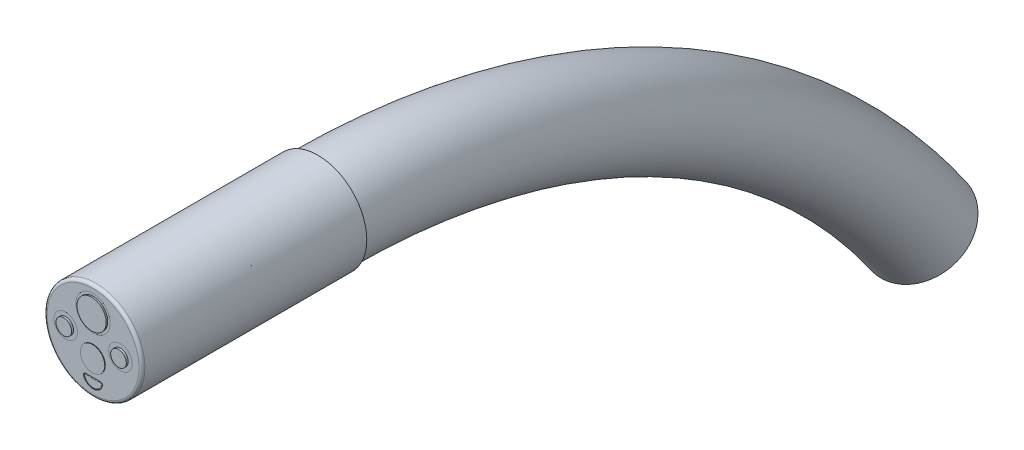
SolidWorks part; units mm, degrees
note: The reader was unsure of these and kept them because the rebuilt part matched: shared geometry of "Sketch", "Sketch", "Sketch", "Sketch", "Sketch", "Sketch", "Sketch", "Sketch", "Sketch", "Sketch".
ref_plane "Front" through (0, 0, 0) normal (0, 0, 1) x (1, 0, 0)
ref_plane "Top" through (0, 0, 0) normal (0, 1, 0) x (1, 0, 0)
ref_plane "Right" through (0, 0, 0) normal (1, 0, 0) x (0, 0, -1)
sketch "Sketch1" plane through (0, 0, 0) normal (0, 0, 1) x (1, 0, 0)
  circle A0 centre (0, 0) radius 5
  dimension "D1" = 10
extrude "Extrude1" add sketch "Sketch1" along normal blind 23
sketch "Sketch2" plane through (0, 0, 23) normal (0, 0, 1) x (1, 0, 0)
  line L0 (-0.7746, -3.2) -> (0.7746, -3.2)
  line L1 (0, 0) -> (0, 1.8906) construction
  circle A0 centre (0, 2.5) radius 1.5
  circle A1 centre (2.8, 0) radius 1
  circle A2 centre (0, -1.5) radius 1.25
  arc A3 (-0.9682, -3.45) -> (0.9682, -3.45) centre (0, -3.2) ccw
  arc A4 (-0.7746, -3.2) -> (-0.9682, -3.45) centre (-0.7746, -3.4) ccw
  arc A5 (0.7746, -3.2) -> (0.9682, -3.45) centre (0.7746, -3.4) cw
  circle A6 centre (-2.8, 0) radius 1
  point P13 (-1, -3.2)
  point P16 (1, -3.2)
  dimension "D1" = 3
  dimension "D2" = 2
  dimension "D3" = 2.5
  dimension "D7" = 2
  dimension "D9" = 0.2
  dimension "D10" = 0.2
  dimension "D4" = 2.5
  dimension "D5" = 2.8
  dimension "D6" = 1.5
  dimension "D8" = 3.2
extrude "Extrude2" cut sketch "Sketch2" against normal blind 40
sketch "Sketch3" plane through (0, 0, 0) normal (1, 0, 0) x (0, 0, -1)
  line L0 (0, -5) -> (0, 5) construction
  line L1 (0, 4) -> (-10.95, 4)
  line L2 (0, 4) -> (0, 3.3)
  line L3 (0, 3.3) -> (-10.95, 3.3)
  line L4 (-10.95, 4) -> (-10.95, 3.3)
  line L5 (0, 2.5) -> (-23, 2.5) construction
  line L6 (-23, 5) -> (-23, -5) construction
  line L7 (-10.95, 4) -> (-13.45, 4)
  line L8 (-10.95, 4) -> (-10.95, 4.25)
  line L9 (-10.95, 4.25) -> (-13.45, 4.25)
  line L10 (-13.45, 4) -> (-13.45, 4.25)
  line L11 (-4.2338, 2.5) -> (-7.2586, 2.5) construction
  dimension "D1" = 0.7
  dimension "D2" = 1.5
  dimension "D3" = 0.25
  dimension "D4" = 2.5
  dimension "D5" = 9.55
revolve "Revolve1" add sketch "Sketch3" angle 360 about L11
revolve "Cut-Revolve1" cut sketch "Sketch" angle 360 about L11
sketch "Sketch" plane through (0, 0, 0) normal (1, 0, 0) x (0, 0, -1) same geometry as "Sketch3"
sketch "Sketch4" plane through (0, 0, 23) normal (0, 0, 1) x (1, 0, 0)
  circle A2 centre (0, 2.5) radius 1.75
  circle A3 centre (0, 2.5) radius 1.75
  dimension "D1" = 0.25
extrude "Extrude3" cut sketch "Sketch4" against normal up to surface (9.55 mm away) up to face at (-1.75, 2.5, 13.45)
ref_plane "Plane1" through (-2.8, 0, 0) normal (1, 0, 0) x (0, 0, -1)
sketch "Sketch5" plane through (-2.8, 0, 0) normal (1, 0, 0) x (0, 0, -1)
  line L0 (-23, 5) -> (-23, -5) construction
  line L1 (-23, 1.2) -> (-22.8, 1.2)
  line L2 (-23, 1.2) -> (-23, 1)
  line L3 (-23, 1) -> (-22.8, 1)
  line L4 (-22.8, 1.2) -> (-22.8, 1)
  line L5 (-23, 0) -> (0, 0) construction
  line L6 (-23, 0) -> (-22.2268, 0) construction
  dimension "D1" = 1
  dimension "D2" = 0.2
  dimension "D3" = 0.2
revolve "Cut-Revolve2" cut sketch "Sketch5" angle 360 about L6
mirror "Mirror1" about plane through (0, 0, 0) normal (1, 0, 0) of "Cut-Revolve2"
sketch "Sketch6" plane through (0, 0, 23) normal (0, 0, 1) x (1, 0, 0)
  line L0 (0.7746, -3.2) -> (-0.7746, -3.2) construction
  line L1 (0.7746, -3.2) -> (-0.7746, -3.2)
  arc A0 (-0.7746, -3.2) -> (-0.9682, -3.45) centre (-0.7746, -3.4) ccw construction
  arc A1 (0.9682, -3.45) -> (0.7746, -3.2) centre (0.7746, -3.4) ccw construction
  arc A2 (-0.9682, -3.45) -> (0.9682, -3.45) centre (0, -3.2) ccw construction
  arc A3 (-0.7746, -3.2) -> (-0.9682, -3.45) centre (-0.7746, -3.4) ccw
  arc A4 (0.9682, -3.45) -> (0.7746, -3.2) centre (0.7746, -3.4) ccw
  arc A5 (-0.9682, -3.45) -> (0.9682, -3.45) centre (0, -3.2) ccw
extrude "Extrude4" add sketch "Sketch6" against normal blind 25 separate body
fillet "Fillet2" radius 0.1 4 edges at (0.9327, -3.2775, 23) (0, -4.2, 23) (-0.9327, -3.2775, 23) (0, -3.2, 23)
fillet "Fillet3" radius 0.3 1 edges at (5, 0, 23)
sketch "Sketch7" plane through (0, 0, 0) normal (1, 0, 0) x (0, 0, -1)
  line L0 (-30.3416, 2.5) -> (0.6495, 2.5) construction
  line L1 (-22.85, 2.5) -> (-22.85, 7.6097) construction
  line L2 (-23.15, 4) -> (-22.55, 4)
  line L3 (-23.15, 4) -> (-23.15, 2.5)
  line L4 (-23.15, 2.5) -> (-22.55, 2.5)
  line L5 (-22.55, 4) -> (-22.55, 2.5)
  line L6 (-30.3416, 4.25) -> (-30.3416, 0.75) construction
  line L7 (-23, 2.5) -> (-10.95, 2.5) construction
  line L8 (-23, 4.25) -> (-23, 0.75) construction
  line L9 (-18.6379, 2.5) -> (-18.85, 2.5)
  line L10 (-22.55, 3.7) -> (-22.15, 3.7)
  line L11 (-22.55, 3.7) -> (-22.55, 2.5)
  line L12 (-22.55, 2.5) -> (-22.15, 2.5)
  line L13 (-22.15, 3.7) -> (-22.15, 2.5)
  line L14 (-21.85, 2.5) -> (-18.85, 2.5)
  line L15 (-21.85, 2.5) -> (-21.85, 3.7)
  line L16 (-21.85, 3.7) -> (-18.85, 3.7)
  line L17 (-18.85, 2.5) -> (-18.85, 3.7)
  line L18 (-14.75, 2.5) -> (-14.2542, 2.5)
  line L19 (-18.55, 2.5) -> (-16.55, 2.5)
  line L20 (-18.55, 2.5) -> (-18.55, 3.7)
  line L21 (-18.55, 3.7) -> (-16.55, 3.7)
  line L22 (-16.55, 2.5) -> (-16.55, 3.7)
  line L23 (-16.05, 2.5) -> (-14.75, 2.5)
  line L24 (-16.05, 2.5) -> (-16.05, 3.7)
  line L25 (-16.05, 3.7) -> (-14.75, 3.7)
  line L26 (-14.75, 2.5) -> (-14.75, 3.7)
  line L27 (-14.75, 3.7) -> (-13.75, 3.7)
  line L28 (-13.75, 3.7) -> (-13.75, 2.5)
  line L29 (-13.75, 2.5) -> (-14.2542, 2.5)
  line L30 (-10.95, 2.5) -> (0, 2.5) construction
  line L31 (-16.2559, 2.5) -> (-16.05, 2.5)
  line L32 (-13.45, 2.5) -> (-12.65, 2.5)
  line L33 (-13.45, 2.5) -> (-13.45, 3.8)
  line L34 (-13.45, 3.8) -> (-12.65, 3.8)
  line L35 (-12.65, 2.5) -> (-12.65, 3.8)
  line L36 (-12.65, 2.5) -> (-12.15, 2.5)
  line L37 (-12.65, 2.5) -> (-12.65, 3.5)
  line L38 (-12.65, 3.5) -> (-12.15, 3.5)
  line L39 (-12.15, 2.5) -> (-12.15, 3.5)
  arc A0 (-22.55, 3.2141) -> (-22.85, 2.5) centre (-21.85, 2.5) ccw
  arc A1 (-18.85, 3.7) -> (-18.6379, 2.5) centre (-22.1379, 2.5) cw
  arc A2 (-14.75, 3.7) -> (-14.2542, 2.5) centre (-15.9542, 2.5) cw
  arc A3 (-16.05, 3.7) -> (-16.2559, 2.5) centre (-12.6559, 2.5) ccw
  point P12 (-30.3416, 2.5)
  dimension "D3" = 1
  dimension "D10" = 3.5
  dimension "D17" = 1.7
  dimension "D24" = 3.6
  dimension "D1" = 1.5
  dimension "D2" = 0.6
  dimension "D4" = 0.45
  dimension "D5" = 1.2
  dimension "D6" = 0.4
  dimension "D7" = 1.2
  dimension "D8" = 0.3
  dimension "D9" = 3
  dimension "D11" = 1.2
  dimension "D12" = 2
  dimension "D13" = 0.3
  dimension "D14" = 1.2
  dimension "D15" = 1.3
  dimension "D16" = 0.5
  dimension "D18" = 1
  dimension "D19" = 1.3
  dimension "D20" = 0.8
  dimension "D21" = 0.3
  dimension "D22" = 1
  dimension "D23" = 0.5
revolve "Revolve2" add sketch "Sketch7" angle 360 about L0
revolve "Revolve3" add sketch "Sketch" angle 360 about L0
sketch "Sketch" plane through (0, 0, 0) normal (1, 0, 0) x (0, 0, -1) same geometry as "Sketch7"
revolve "Revolve4" add sketch "Sketch" angle 360 about L14
sketch "Sketch" plane through (0, 0, 0) normal (1, 0, 0) x (0, 0, -1) same geometry as "Sketch7"
revolve "Revolve5" add sketch "Sketch" angle 360 about L19
sketch "Sketch" plane through (0, 0, 0) normal (1, 0, 0) x (0, 0, -1) same geometry as "Sketch7"
revolve "Revolve6" add sketch "Sketch" angle 360 about L23
sketch "Sketch" plane through (0, 0, 0) normal (1, 0, 0) x (0, 0, -1) same geometry as "Sketch7"
revolve "Revolve7" add sketch "Sketch" angle 360 about L29
sketch "Sketch" plane through (0, 0, 0) normal (1, 0, 0) x (0, 0, -1) same geometry as "Sketch7"
revolve "Revolve8" add sketch "Sketch" angle 360 about L32
sketch "Sketch" plane through (0, 0, 0) normal (1, 0, 0) x (0, 0, -1) same geometry as "Sketch7"
revolve "Revolve9" add sketch "Sketch" angle 360 about L36
sketch "Sketch" plane through (0, 0, 0) normal (1, 0, 0) x (0, 0, -1) same geometry as "Sketch7"
sketch "Sketch9" plane through (0, 0, 0) normal (1, 0, 0) x (0, 0, -1)
  line L0 (-22.55, 1) -> (-22.55, 4) construction
  line L1 (-22.55, 4) -> (-18.55, 4)
  line L2 (-22.55, 4) -> (-22.55, 3.7)
  line L3 (-22.55, 3.7) -> (-18.55, 3.7)
  line L4 (-18.55, 4) -> (-18.55, 3.7)
  line L5 (-18.55, 3.7) -> (-18.55, 1.3) construction
  line L6 (-22.55, 4) -> (-23.15, 4) construction
  line L7 (-22.15, 3.7) -> (-22.55, 3.7) construction
  line L8 (-21.85, 3.7) -> (-21.85, 1.3) construction
  line L9 (-22.15, 3.7) -> (-21.85, 3.7)
  line L10 (-22.15, 3.7) -> (-22.15, 3.5)
  line L11 (-22.15, 3.5) -> (-21.85, 3.5)
  line L12 (-21.85, 3.7) -> (-21.85, 3.5)
  line L13 (-22.15, 1.3) -> (-22.15, 3.7) construction
  line L16 (-18.55, 4) -> (-18.55, 3.85)
  line L19 (-20.6571, 2.5) -> (-24.8785, 2.5) construction
  line L20 (-18.85, 2.5) -> (-21.85, 2.5) construction
  line L21 (-16.55, 2.5) -> (-18.55, 2.5) construction
  line L22 (-22.2916, 2.5) -> (-23.5168, 2.5) construction
  line L25 (-18.55, 3.85) -> (-18.55, 3.7)
  line L28 (-18.55, 3.85) -> (-13.75, 3.85)
  line L29 (-18.55, 3.85) -> (-18.55, 3.7)
  line L30 (-18.55, 3.7) -> (-13.75, 3.7)
  line L31 (-13.75, 3.85) -> (-13.75, 3.7)
  dimension "D1" = 0.2
  dimension "D2" = 0.15
revolve "Revolve11" add sketch "Sketch9" angle 360 about L19
sketch "Sketch10" plane through (0, 0, 0) normal (1, 0, 0) x (0, 0, -1)
  line L0 (-13.75, 3.85) -> (-18.55, 3.85) construction
  line L1 (-18.55, 4) -> (-13.45, 4)
  line L2 (-18.55, 4) -> (-18.55, 3.85)
  line L3 (-18.55, 3.85) -> (-13.45, 3.85)
  line L4 (-13.45, 4) -> (-13.45, 3.85)
  line L5 (-13.45, 3.8) -> (-13.45, 1.2) construction
  line L6 (-13.75, 1.15) -> (-13.75, 3.85) construction
  line L7 (-13.45, 3.85) -> (-13.75, 3.85)
  line L8 (-13.45, 3.85) -> (-13.45, 3.6)
  line L9 (-13.45, 3.6) -> (-13.75, 3.6)
  line L10 (-13.75, 3.85) -> (-13.75, 3.6)
  dimension "D1" = 0.25
revolve "Revolve12" add sketch "Sketch10" angle 360 about axis through (0, 2.5, 20.6571) along (0, 0, -1)
sketch "Sketch11" plane through (0, 0, 0) normal (1, 0, 0) x (0, 0, -1)
  line L0 (-12.65, 3.8) -> (-13.45, 3.8) construction
  line L1 (-13.45, 3.8) -> (-11.95, 3.8)
  line L2 (-13.45, 3.8) -> (-13.45, 4.25)
  line L3 (-13.45, 4.25) -> (-11.95, 4.25)
  line L4 (-11.95, 3.8) -> (-11.95, 4.25)
  line L5 (-11.95, 4.25) -> (-10.95, 4.25)
  line L6 (-11.95, 4.25) -> (-11.95, 4.02)
  line L7 (-11.95, 4.02) -> (-10.95, 4.02)
  line L8 (-10.95, 4.25) -> (-10.95, 4.02)
  line L9 (-12.65, 3.8) -> (-12.15, 3.8)
  line L10 (-12.65, 3.8) -> (-12.65, 3.5)
  line L11 (-12.65, 3.5) -> (-12.15, 3.5)
  line L12 (-12.15, 3.8) -> (-12.15, 3.5)
  line L13 (-21.85, 2.5) -> (-13.75, 2.5) construction
  line L14 (-12.65, 1.2) -> (-12.65, 3.8) construction
  line L15 (-12.15, 1.5) -> (-12.15, 3.5) construction
  line L16 (-11.95, 3.8) -> (-12.15, 3.8)
  line L17 (-11.95, 3.8) -> (-11.95, 3.45)
  line L18 (-11.95, 3.45) -> (-12.15, 3.45)
  line L19 (-12.15, 3.8) -> (-12.15, 3.45)
  line L20 (-12.15, 2.5) -> (-12.65, 2.5) construction
  line L21 (-17.9017, 2.5) -> (-6.3381, 2.5) construction
  line L22 (-16.55, 2.5) -> (-18.55, 2.5) construction
  line L24 (-11.95, 4.02) -> (-10.95, 4.02)
  line L25 (-11.95, 4.02) -> (-11.95, 2.5)
  line L26 (-11.95, 2.5) -> (-10.95, 2.5)
  line L27 (-10.95, 4.02) -> (-10.95, 2.5)
  dimension "D1" = 1.5
  dimension "D2" = 1
  dimension "D3" = 1.75
  dimension "D4" = 0.95
  dimension "D5" = 0.23
  dimension "D6" = 1
revolve "Revolve13" add sketch "Sketch11" angle 360 about L21
revolve "Revolve14" add sketch "Sketch" angle 360 about L21
sketch "Sketch" plane through (0, 0, 0) normal (1, 0, 0) x (0, 0, -1) same geometry as "Sketch11"
sketch "Sketch13" plane through (0, 0, 0) normal (1, 0, 0) x (0, 0, -1)
  line L0 (-18.55, 3.7) -> (-18.55, 1.3) construction
  line L1 (-18.85, 3.7) -> (-21.85, 3.7) construction
  line L2 (-16.55, 1.3) -> (-16.55, 3.7) construction
  line L3 (-16.55, 3.7) -> (-18.55, 3.7) construction
  circle A0 centre (-18.6754, 3.5746) radius 0.1254
  arc A1 (-18.85, 1.3) -> (-18.85, 3.7) centre (-22.1379, 2.5) ccw construction
  circle A2 centre (-16.3378, 3.4878) radius 0.2122
  arc A3 (-16.05, 3.7) -> (-16.05, 1.3) centre (-12.6559, 2.5) ccw construction
revolve "Revolve15" add sketch "Sketch13" angle 360
revolve "Revolve16" add sketch "Sketch" angle 360 about axis through (0, 2.5, 18.55) along (0, 0, 1)
sketch "Sketch" plane through (0, 0, 0) normal (1, 0, 0) x (0, 0, -1) same geometry as "Sketch13"
sketch "Sketch15" plane through (0, 0, 23) normal (0, 0, 1) x (1, 0, 0)
  circle A0 centre (0, 2.5) radius 1.5 construction
  circle A1 centre (0, 2.5) radius 1.5
  circle A2 centre (0, 2.5) radius 1.75 construction
  circle A3 centre (0, 2.5) radius 1.75
extrude "Extrude5" add sketch "Sketch15" against normal up to surface (9.55 mm away) separate body up to face at (1.75, 2.5, 13.45)
sketch "Sketch16" plane through (0, 0, 10.95) normal (0, 0, -1) x (-1, 0, 0)
  circle A0 centre (0, 2.5) radius 0.6
  dimension "D1" = 1.2
extrude "Extrude6" add sketch "Sketch16" along normal blind 15 separate body
sketch "Sketch17" plane through (0, 0, 23) normal (0, 0, 1) x (1, 0, 0)
  circle A0 centre (0, -1.5) radius 1.25 construction
  circle A1 centre (0, -1.5) radius 1.25
extrude "Extrude7" add sketch "Sketch17" against normal blind 0.5 from offset 0.05 separate body
sketch "Sketch18" plane through (0, 0, 22.55) normal (0, 0, -1) x (-1, 0, 0)
  circle A0 centre (0, -1.5) radius 0.9
  dimension "D1" = 1.8
extrude "Extrude8" add sketch "Sketch18" along normal blind 25 separate body
sketch "Sketch19" plane through (-2.8, 0, 0) normal (1, 0, 0) x (0, 0, -1)
  line L0 (0, 0) -> (-22.8, 0) construction
  line L1 (-23.2, 0.8) -> (-19.7, 0.8)
  line L2 (-23.2, 0.8) -> (-23.2, 0)
  line L3 (-23.2, 0) -> (-19.7, 0)
  line L4 (-19.7, 0.8) -> (-19.7, 0)
  line L5 (-23, 4.7) -> (-23, -4.7) construction
  line L7 (-19.7, 0) -> (0, 0)
  line L8 (-19.7, 0) -> (-19.7, 0.25)
  line L9 (-19.7, 0.25) -> (0, 0.25)
  line L10 (0, 0) -> (0, 0.25)
  dimension "D1" = 0.2
  dimension "D2" = 0.8
  dimension "D3" = 3.5
  dimension "D4" = 0.25
revolve "Revolve17" add sketch "Sketch19" angle 360 about L3
sketch "Sketch20" plane through (-2.8, 0, 0) normal (1, 0, 0) x (0, 0, -1)
  line L0 (-19.7, -0.8) -> (-19.7, 0.8) construction
  line L5 (-22.8, 0.8) -> (-19.5, 0.8)
  line L6 (-23, 1.2) -> (-23, -1.2) construction
  line L7 (-23, 1.2) -> (-22.8, 1.2)
  line L8 (-23, 1.2) -> (-23, 0.8)
  line L9 (-23, 0.8) -> (-22.8, 0.8)
  line L10 (-22.8, 1.2) -> (-22.8, 0.8)
  line L11 (-23, 4.7) -> (-23, -4.7) construction
  line L12 (0, 0) -> (-22.8, 0) construction
  line L13 (-22.8, 0.8) -> (-22.8, 1)
  line L14 (-22.8, 1) -> (-19.5, 1)
  line L15 (-19.5, 0.8) -> (-19.5, 1)
  line L16 (-19.5, 0.8) -> (-19.7, 0.8)
  line L17 (-19.5, 0.8) -> (-19.5, 0.25)
  line L18 (-19.5, 0.25) -> (-19.7, 0.25)
  line L19 (-19.7, 0.8) -> (-19.7, 0.25)
  line L20 (-18.4255, 0) -> (-25.7788, 0) construction
  dimension "D1" = 0.8
  dimension "D2" = 1.2
  dimension "D3" = 0.2
  dimension "D4" = 3.5
  dimension "D5" = 1
  dimension "D6" = 0.25
revolve "Revolve18" add sketch "Sketch20" angle 360 about L20
ref_plane "Plane2" through (2.8, 0, 0) normal (1, 0, 0) x (0, 0, -1)
sketch "Sketch21" plane through (2.8, 0, 0) normal (1, 0, 0) x (0, 0, -1)
  line L0 (0, 0) -> (0, 0.25) construction
  line L1 (-19.7, 0) -> (0, 0) construction
  line L2 (-19.7, 0.25) -> (0, 0.25) construction
  line L3 (-19.7, 0.8) -> (-19.7, 0) construction
  line L4 (-23.2, 0) -> (-19.7, 0) construction
  line L5 (-23.2, 0.8) -> (-23.2, 0) construction
  line L6 (-23.2, 0.8) -> (-19.7, 0.8) construction
  line L7 (0, 0) -> (0, 0.25)
  line L8 (-19.7, 0) -> (0, 0)
  line L9 (-19.7, 0.25) -> (0, 0.25)
  line L10 (-19.7, 0.8) -> (-19.7, 0)
  line L11 (-23.2, 0) -> (-19.7, 0)
  line L12 (-23.2, 0.8) -> (-23.2, 0)
  line L13 (-23.2, 0.8) -> (-19.7, 0.8)
revolve "Revolve19" add sketch "Sketch21" angle 360 about L11
sketch "Sketch22" plane through (2.8, 0, 0) normal (1, 0, 0) x (0, 0, -1)
  line L0 (-18.4255, 0) -> (-25.7788, 0) construction
  line L1 (-18.4255, 0) -> (-25.7788, 0) construction
  line L2 (-19.5, 0.25) -> (-19.7, 0.25) construction
  line L3 (-19.7, 0.8) -> (-19.7, 0.25) construction
  line L4 (-19.5, 0.8) -> (-19.5, 0.25) construction
  line L5 (-19.5, 0.8) -> (-19.5, 1) construction
  line L6 (-22.8, 0.8) -> (-19.5, 0.8) construction
  line L7 (-22.8, 1) -> (-19.5, 1) construction
  line L8 (-23, 1.2) -> (-22.8, 1.2) construction
  line L9 (-23, 1.2) -> (-23, 0.8) construction
  line L10 (-23, 0.8) -> (-22.8, 0.8) construction
  line L11 (-22.8, 1.2) -> (-22.8, 0.8) construction
  line L12 (-19.5, 0.25) -> (-19.7, 0.25)
  line L13 (-19.7, 0.8) -> (-19.7, 0.25)
  line L14 (-19.5, 0.8) -> (-19.5, 0.25)
  line L15 (-19.5, 0.8) -> (-19.5, 1)
  line L16 (-22.8, 0.8) -> (-19.5, 0.8)
  line L17 (-22.8, 1) -> (-19.5, 1)
  line L18 (-23, 1.2) -> (-22.8, 1.2)
  line L19 (-23, 1.2) -> (-23, 0.8)
  line L20 (-23, 0.8) -> (-22.8, 0.8)
  line L21 (-22.8, 1.2) -> (-22.8, 0.8)
revolve "Revolve20" add sketch "Sketch22" angle 360 about L1
sketch "Sketch23" plane through (0, 0, 0) normal (0, 0, -1) x (-1, 0, 0)
  circle A0 centre (0, 0) radius 4.7
  circle A1 centre (0, 0) radius 4.25
  dimension "D1" = 9.4
  dimension "D2" = 8.5
sketch "Sketch24" plane through (0, 0, 0) normal (1, 0, 0) x (0, 0, -1)
  line L0 (0, 0) -> (-4.019, 0) construction
  line L1 (0, 0) -> (-22.8, 0) construction
  arc A0 (0, 0) -> (61.4492, -32) centre (0, -75) cw
  dimension "D1" = 75
  dimension "D2" = 32
sweep "Sweep1" add profiles "Sketch23" path "Sketch24"
